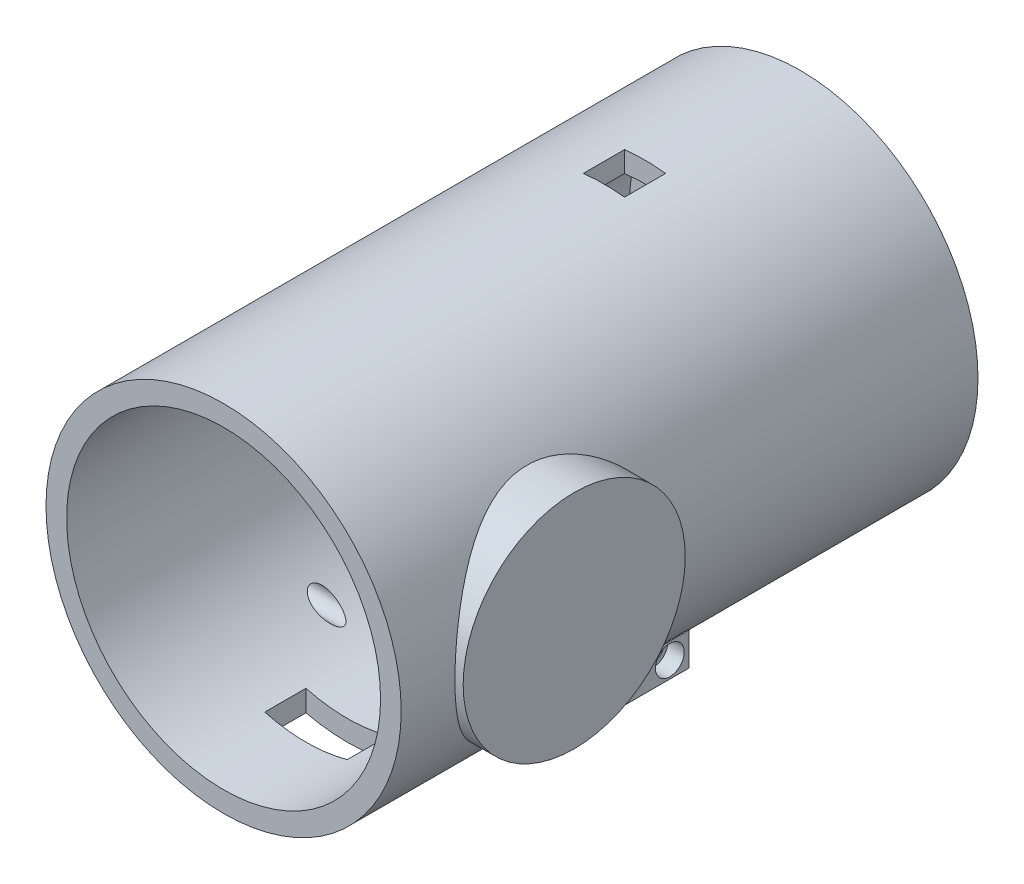
SolidWorks part; units mm, degrees
other "Markup1"
sketch "Sketch14" plane through (-43.1, 43.1, 140) normal (-0.1765, 0.0048, 0.9843) x (0.9842, -0.0149, 0.1765)
other "Markup2"
sketch "Sketch23" plane through (45.1, -43.1, 140) normal (0.9491, -0.0629, 0.3087) x (0.311, 0.031, -0.9499)
ref_plane "Front Plane" through (0, 0, 0) normal (0, 0, 1) x (1, 0, 0)
ref_plane "Top Plane" through (0, 0, 0) normal (0, 1, 0) x (1, 0, 0)
ref_plane "Right Plane" through (0, 0, 0) normal (1, 0, 0) x (0, 0, -1)
sketch "Sketch1" plane through (0, 0, 0) normal (0, 0, 1) x (1, 0, 0)
  circle A1 centre (0, 0) radius 43.1
  dimension "D1" = 86.2
extrude "Main Body" add sketch "Sketch1" along normal blind 140
ref_plane "Plane1" through (0, 43.1, 0) normal (0, 1, 0) x (1, 0, 0)
sketch "Sketch6" plane through (0, 43.1, 0) normal (0, 1, 0) x (1, 0, 0)
  line L2 (-5, -47.7) -> (5, -47.7)
  line L3 (-5, -47.7) -> (-5, -37.7)
  line L4 (-5, -37.7) -> (5, -37.7)
  line L5 (5, -47.7) -> (5, -37.7)
  line L6 (-5, -47.7) -> (5, -37.7) construction
  line L7 (-5, -37.7) -> (5, -47.7) construction
  point P2 (0, -42.7)
  dimension "D2" = 10
  dimension "D1" = 42.7
  dimension "D3" = 10
extrude "Cut-Extrude3" cut sketch "Sketch6" against normal through all
ref_plane "Plane2" through (45.1, 0, 0) normal (1, 0, 0) x (0, 0, -1)
sketch "Sketch8" plane through (45.1, 0, 0) normal (1, 0, 0) x (0, 0, -1)
  circle A0 centre (-100, 0) radius 26.95
  dimension "D1" = 53.9
  dimension "D2" = 100
extrude "Boss-Extrude2" add sketch "Sketch8" against normal blind 20
mirror "Mirror1" [suppressed] about plane through (0, 0, 0) normal (1, 0, 0)
sketch "Sketch5" plane through (0, 0, 140) normal (0, 0, 1) x (1, 0, 0)
  circle A0 centre (0, 0) radius 31.75
  dimension "D1" = 63.5
sketch "Sketch2" plane through (0, 0, 140) normal (0, 0, 1) x (1, 0, 0)
  circle A0 centre (0, 0) radius 38.1
  dimension "D1" = 76.2
extrude "Cut-Extrude4" cut sketch "Sketch5" against normal through all
extrude "Cut-Extrude5" cut sketch "Sketch2" against normal blind 135
sketch "Sketch9" plane through (0, 0, 5) normal (0, 0, 1) x (1, 0, 0)
  circle A0 centre (0, 0) radius 38.1
  circle A1 centre (0, 0) radius 36.44
  dimension "D1" = 76.2
  dimension "D2" = 1.66
extrude "Boss-Extrude3" add sketch "Sketch9" along normal blind 10
sketch "Sketch10" plane through (0, 0, 0) normal (0, 1, 0) x (1, 0, 0)
  line L0 (43.1, 0) -> (-43.1, 0) construction
  line L1 (-10, -120) -> (10, -120)
  line L2 (-10, -120) -> (-10, -110)
  line L3 (-10, -110) -> (10, -110)
  line L4 (10, -120) -> (10, -110)
  line L5 (-10, -120) -> (10, -110) construction
  line L6 (-10, -110) -> (10, -120) construction
  point P0 (0, -115)
  point P7 (-10, -115)
  dimension "D1" = 110
  dimension "D2" = 10
  dimension "D3" = 20
extrude "Motor Wire Hole" cut sketch "Sketch10" against normal through all
ref_plane "Plane3" through (26, 0, 0) normal (1, 0, 0) x (0, 0, -1)
ref_plane "Plane4" through (-26, 0, 0) normal (1, 0, 0) x (0, 0, -1)
sketch "Sketch17" plane through (26, 0, 0) normal (1, 0, 0) x (0, 0, -1)
  line L0 (0, -43.1) -> (0, 43.1) construction
  line L1 (-100, -36) -> (-60, -36)
  line L2 (-100, -36) -> (-100, -28)
  line L3 (-100, -28) -> (-60, -28)
  line L4 (-60, -36) -> (-60, -28)
  dimension "D1" = 60
  dimension "D2" = 40
  dimension "D3" = 28
  dimension "D4" = 8
extrude "Boss-Extrude4" add sketch "Sketch17" along normal blind 7
sketch "Sketch20" plane through (-26, 0, 0) normal (1, 0, 0) x (0, 0, -1)
  line L1 (-60, -28) -> (-100, -28)
  line L2 (-60, -28) -> (-60, -36)
  line L3 (-60, -36) -> (-100, -36)
  line L4 (-100, -28) -> (-100, -36)
  dimension "D1" = 60
  dimension "D2" = 40
  dimension "D3" = 28
  dimension "D4" = 8
extrude "Boss-Extrude5" add sketch "Sketch20" against normal blind 7
sketch "Sketch21" plane through (-26, 0, 0) normal (1, 0, 0) x (0, 0, -1)
  line L0 (-60, -36) -> (-60, -28) construction
  line L1 (-100, -36) -> (-60, -36)
  line L2 (-100, -36) -> (-100, -32)
  line L3 (-100, -32) -> (-60, -32)
  line L4 (-60, -36) -> (-60, -32)
extrude "Boss-Extrude6" add sketch "Sketch21" along normal blind 3
sketch "Sketch22" plane through (26, 0, 0) normal (-1, 0, 0) x (0, 0, 1)
  line L0 (100, -36) -> (100, -28) construction
  line L1 (60, -36) -> (100, -36)
  line L2 (60, -36) -> (60, -32)
  line L3 (60, -32) -> (100, -32)
  line L4 (100, -36) -> (100, -32)
extrude "Boss-Extrude7" add sketch "Sketch22" along normal blind 3
sketch "Sketch11" plane through (0, 0, 0) normal (1, 0, 0) x (0, 0, -1)
  circle A0 centre (-64.7, -32) radius 2.5
  circle A1 centre (-94.7, -32) radius 2.5
  dimension "D3" = 5
  dimension "D1" = 64.7
  dimension "D2" = 32
  dimension "D4" = 30
extrude "Cut-Extrude7" cut sketch "Sketch11" against normal through all both and the other way through all
sketch "Sketch12" plane through (26, 0, 0) normal (1, 0, 0) x (0, 0, -1)
  circle A0 centre (-64.7, -32) radius 3.5
  circle A1 centre (-94.7, -32) radius 3.5
  dimension "D1" = 7
extrude "Cut-Extrude8" [suppressed] cut sketch "Sketch12" along normal through all
sketch "Sketch13" plane through (-26, 0, 0) normal (1, 0, 0) x (0, 0, -1)
  line L0 (-92.6793, -28.5) -> (-96.7207, -28.5)
  line L1 (-62.6793, -28.5) -> (-60.6585, -32)
  line L2 (-60.6585, -32) -> (-62.6793, -35.5)
  line L3 (-62.6793, -35.5) -> (-66.7207, -35.5)
  line L4 (-66.7207, -35.5) -> (-68.7415, -32)
  line L5 (-68.7415, -32) -> (-66.7207, -28.5)
  line L6 (-66.7207, -28.5) -> (-62.6793, -28.5)
  line L7 (-96.7207, -28.5) -> (-98.7415, -32)
  line L8 (-98.7415, -32) -> (-96.7207, -35.5)
  line L9 (-96.7207, -35.5) -> (-92.6793, -35.5)
  line L10 (-92.6793, -35.5) -> (-90.6585, -32)
  line L11 (-90.6585, -32) -> (-92.6793, -28.5)
  circle A0 centre (-94.7, -32) radius 3.5 construction
  circle A1 centre (-64.7, -32) radius 3.5 construction
  dimension "D1" = 7
extrude "Cut-Extrude9" [suppressed] cut sketch "Sketch13" against normal through all
sketch "Sketch25" plane through (-33, 0, 0) normal (-1, 0, 0) x (0, 0, 1)
  line L0 (66.7207, -28.5) -> (62.6793, -28.5)
  line L1 (96.7207, -28.5) -> (98.7415, -32)
  line L2 (98.7415, -32) -> (96.7207, -35.5)
  line L3 (96.7207, -35.5) -> (92.6793, -35.5)
  line L4 (92.6793, -35.5) -> (90.6585, -32)
  line L5 (90.6585, -32) -> (92.6793, -28.5)
  line L6 (92.6793, -28.5) -> (96.7207, -28.5)
  line L7 (62.6793, -28.5) -> (60.6585, -32)
  line L8 (60.6585, -32) -> (62.6793, -35.5)
  line L9 (62.6793, -35.5) -> (66.7207, -35.5)
  line L10 (66.7207, -35.5) -> (68.7415, -32)
  line L11 (68.7415, -32) -> (66.7207, -28.5)
  circle A0 centre (64.7, -32) radius 3.5 construction
  circle A1 centre (94.7, -32) radius 3.5 construction
  circle A2 centre (64.7, -32) radius 2.5 construction
  point P18 (0, 0)
  dimension "D1" = 7
  dimension "D2" = 30
extrude "Cut-Extrude10" cut sketch "Sketch25" against normal blind 3
sketch "Sketch26" plane through (33, 0, 0) normal (1, 0, 0) x (0, 0, -1)
  circle A0 centre (-64.7, -32) radius 3.5
  circle A1 centre (-94.7, -32) radius 3.5
  circle A2 centre (-94.7, -32) radius 2.5 construction
  circle A3 centre (-64.7, -32) radius 2.5 construction
  point P4 (0, 0)
  dimension "D1" = 7
extrude "Cut-Extrude11" cut sketch "Sketch26" against normal blind 4
